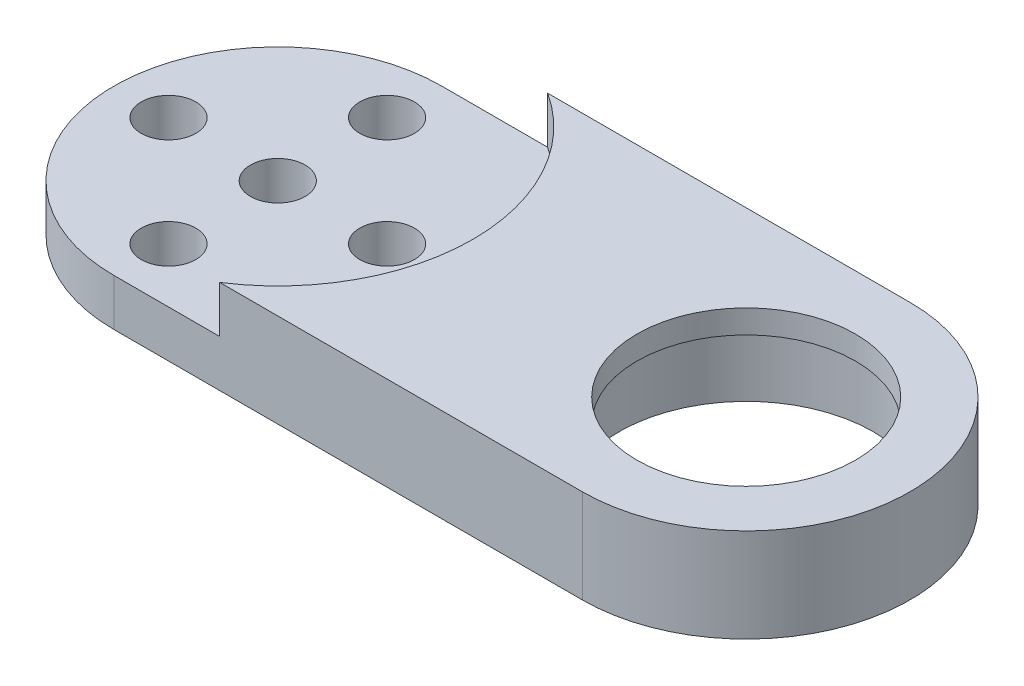
SolidWorks part; units mm, degrees
ref_plane "Front Plane" through (0, 0, 0) normal (0, 0, 1) x (1, 0, 0)
ref_plane "Top Plane" through (0, 0, 0) normal (0, 1, 0) x (1, 0, 0)
ref_plane "Right Plane" through (0, 0, 0) normal (1, 0, 0) x (0, 0, -1)
sketch "Sketch2" plane through (0, 0, 0) normal (0, 1, 0) x (1, 0, 0)
  line L0 (15, 0) -> (-15, 0) construction
  line L1 (15, 10.5) -> (-15, 10.5)
  line L2 (15, -10.5) -> (-15, -10.5)
  arc A0 (15, 10.5) -> (15, -10.5) centre (15, 0) cw
  arc A1 (-15, 10.5) -> (-15, -10.5) centre (-15, 0) ccw
  point P4 (0, 0)
  dimension "D1" = 30
  dimension "D2" = 10.5
  dimension "D3" = 10.5
extrude "Boss-Extrude1" add sketch "Sketch2" along normal blind 6
sketch "Sketch4" plane through (0, 6, 0) normal (0, 1, 0) x (1, 0, 0)
  line L0 (-15, 0) -> (-8, 0) construction
  line L1 (15, 0) -> (-15, 0) construction
  line L2 (-15, 0) -> (-8, 0) construction
  circle A0 centre (-15, 0) radius 1.75
  circle A1 centre (-8, 0) radius 1.75
  circle A2 centre (-15, -7) radius 1.75
  circle A3 centre (-22, 0) radius 1.75
  circle A4 centre (-15, 7) radius 1.75
  dimension "D1" = 3.5
  dimension "D2" = 7
  dimension "D3" = 4
extrude "Servo horn holes" cut sketch "Sketch4" against normal through all
sketch "Sketch5" plane through (0, 0, 0) normal (0, -1, 0) x (-1, 0, 0)
  circle A0 centre (-15, 0) radius 8.15
  dimension "D1" = 16.3
extrude "Bearing press fit" cut sketch "Sketch5" against normal blind 4.5
sketch "Sketch6" plane through (0, 6, 0) normal (0, 1, 0) x (1, 0, 0)
  circle A0 centre (15, 0) radius 10.5
  circle A1 centre (15, 0) radius 7
  dimension "D1" = 14
extrude "Boss-Extrude2" [suppressed] add sketch "Sketch6" along normal blind 2
sketch "Sketch7" plane through (0, 6, 0) normal (0, 1, 0) x (1, 0, 0)
  circle A0 centre (-15, 0) radius 12.5
  dimension "D1" = 25
extrude "Cut-Extrude1" cut sketch "Sketch7" against normal blind 3
sketch "Sketch8" plane through (0, 4.5, 0) normal (0, -1, 0) x (1, 0, 0)
  circle A0 centre (15, 0) radius 7
  dimension "D1" = 14
extrude "Cut-Extrude2" cut sketch "Sketch8" against normal through all
